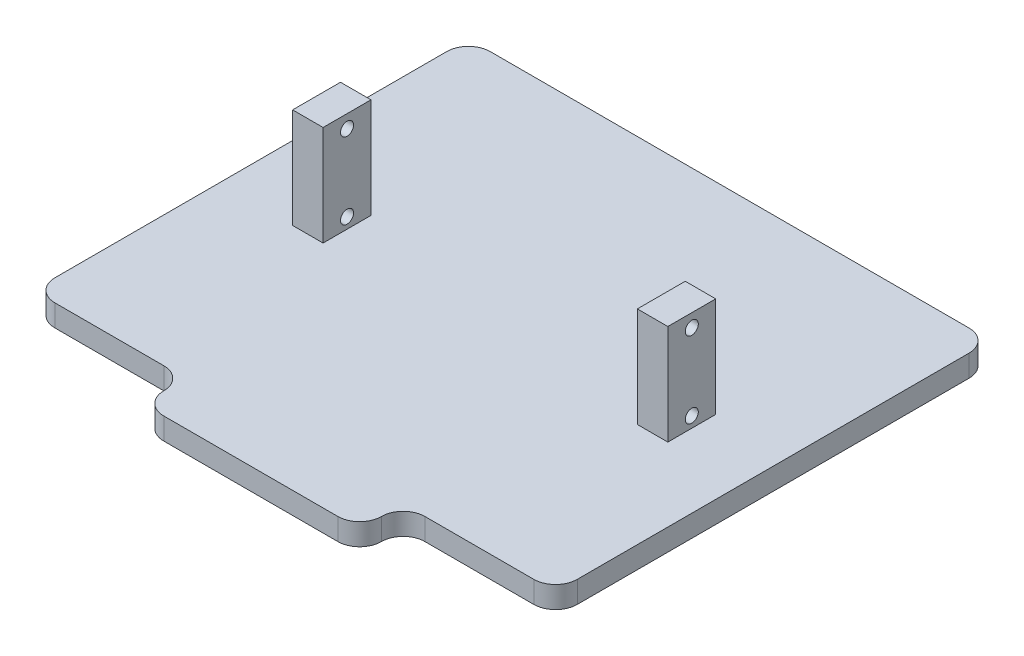
SolidWorks part; units mm, degrees
ref_plane "정면" through (0, 0, 0) normal (0, 0, 1) x (1, 0, 0)
ref_plane "윗면" through (0, 0, 0) normal (0, 1, 0) x (1, 0, 0)
ref_plane "우측면" through (0, 0, 0) normal (1, 0, 0) x (0, 0, -1)
sketch "스케치1" plane through (0, 0, 0) normal (0, 1, 0) x (1, 0, 0)
  line L0 (-25, -50) -> (-60, -50)
  line L1 (60, 50) -> (-60, 50)
  line L2 (60, 50) -> (60, -50)
  line L3 (60, -50) -> (25, -50)
  line L4 (-60, 50) -> (-60, -50)
  line L5 (60, 50) -> (-60, -50) construction
  line L6 (60, -50) -> (-60, 50) construction
  line L7 (25, -60) -> (-25, -60)
  line L8 (25, -60) -> (25, -50)
  line L10 (-25, -60) -> (-25, -50)
  line L11 (25, -60) -> (-25, -50) construction
  line L12 (25, -50) -> (-25, -60) construction
  point P0 (0, 0)
  point P6 (0, -55)
  point P11 (0, 0)
  point P12 (0, 0)
  dimension "D1" = 120
  dimension "D2" = 100
  dimension "D3" = 50
  dimension "D4" = 10
extrude "보스-돌출1" add sketch "스케치1" along normal blind 5
fillet "필렛1" radius 5 8 edges at (60, 2.5, -50) (60, 2.5, 50) (-60, 2.5, -50) (-60, 2.5, 50) (-25, 2.5, 50) (25, 2.5, 50) (25, 2.5, 60) (-25, 2.5, 60)
sketch "스케치2" plane through (0, 5, 0) normal (0, 1, 0) x (1, 0, 0)
  line L0 (-43.1, 27) -> (-43.1, -7.8) construction
  line L1 (-36.1, -7.3) -> (-43.1, -7.3)
  line L2 (-36.1, -7.3) -> (-36.1, 3.7)
  line L3 (-36.1, 3.7) -> (-43.1, 3.7)
  line L4 (-43.1, -7.3) -> (-43.1, 3.7)
  line L5 (-61.9, -3.3) -> (-43.1, -3.3) construction
  line L6 (-43.1, -0.3) -> (-61.9, -0.3) construction
  dimension "D1" = 7
  dimension "D2" = 4
  dimension "D3" = 4
extrude "보스-돌출2" add sketch "스케치2" along normal blind 23 separate body
sketch "스케치3" plane through (-36.1, 0, 0) normal (1, 0, 0) x (0, 0, -1)
  circle A0 centre (-1.8, 7.5) radius 1.5 construction
  circle A1 centre (-1.8, 25) radius 1.5 construction
  circle A4 centre (-1.8, 7.5) radius 1.5
  circle A5 centre (-1.8, 25) radius 1.5
extrude "컷-돌출1" cut sketch "스케치3" against normal through all
mirror "대칭 복사1" about plane through (0, 0, 0) normal (1, 0, 0) of bodies 103
